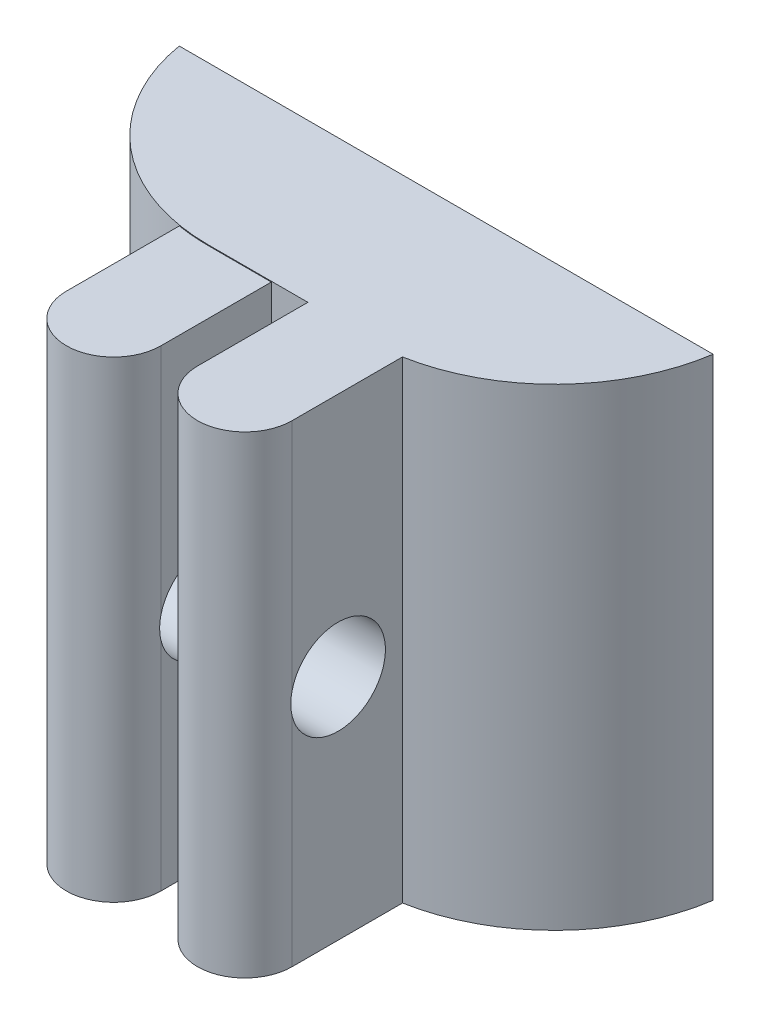
SolidWorks part; units mm, degrees
ref_plane "Front Plane" through (0, 0, 0) normal (0, 0, 1) x (1, 0, 0)
ref_plane "Top Plane" through (0, 0, 0) normal (0, 1, 0) x (1, 0, 0)
ref_plane "Right Plane" through (0, 0, 0) normal (1, 0, 0) x (0, 0, -1)
sketch "Sketch1" plane through (0, 0, 0) normal (0, 0, 1) x (1, 0, 0)
  line L1 (0, 0) -> (-17, 0)
  line L2 (0, 0) -> (0, -15)
  line L3 (0, -15) -> (-17, -15)
  line L4 (-17, 0) -> (-17, -15)
  dimension "D1" = 15
  dimension "D2" = 17
extrude "Boss-Extrude1" add sketch "Sketch1" along normal blind 5
sketch "Sketch2" plane through (0, 0, 5) normal (0, 0, 1) x (1, 0, 0)
  line L0 (0, 0) -> (-17, 0) construction
  line L1 (-7.92, 0) -> (-4.92, 0)
  line L2 (-7.92, 0) -> (-7.92, -15)
  line L3 (-7.92, -15) -> (-4.92, -15)
  line L4 (-4.92, 0) -> (-4.92, -15)
  line L5 (-17, -15) -> (0, -15) construction
  line L7 (-8.5, 0) -> (-8.5, -15) construction
  line L8 (-12.08, -0.0236) -> (-9.08, -0.0236)
  line L9 (-12.08, -0.0236) -> (-12.08, -15)
  line L10 (-12.08, -15) -> (-9.08, -15)
  line L11 (-9.08, -0.0236) -> (-9.08, -15)
  dimension "D1" = 4.92
  dimension "D2" = 3
  dimension "D3" = 4.92
extrude "Boss-Extrude2" add sketch "Sketch2" along normal blind 5
sketch "Sketch4" plane through (-9.08, 0, 0) normal (1, 0, 0) x (0, 0, -1)
  circle A0 centre (-7.0414, -7.7625) radius 1.5
  dimension "D1" = 3
extrude "Cut-Extrude2" cut sketch "Sketch4" against normal through all both and the other way through all
fillet "Fillet1" radius 6 2 edges at (-17, -7.5, 5) (0, -7.5, 5)
fillet "Fillet3" 2 edges at (-12.08, -7.5118, 10) (-9.08, -7.5118, 10) type full round first side face at (-12.08, -6.2625, 7.0414) second side face at (-9.08, -9.2625, 7.0414) middle face at (-10.58, -7.5118, 10)
fillet "Fillet4" 2 edges at (-7.92, -7.5, 10) (-4.92, -7.5, 10) type full round first side face at (-7.92, -6.2625, 7.0414) second side face at (-4.92, -9.2625, 7.0414) middle face at (-6.42, -7.5, 10)
